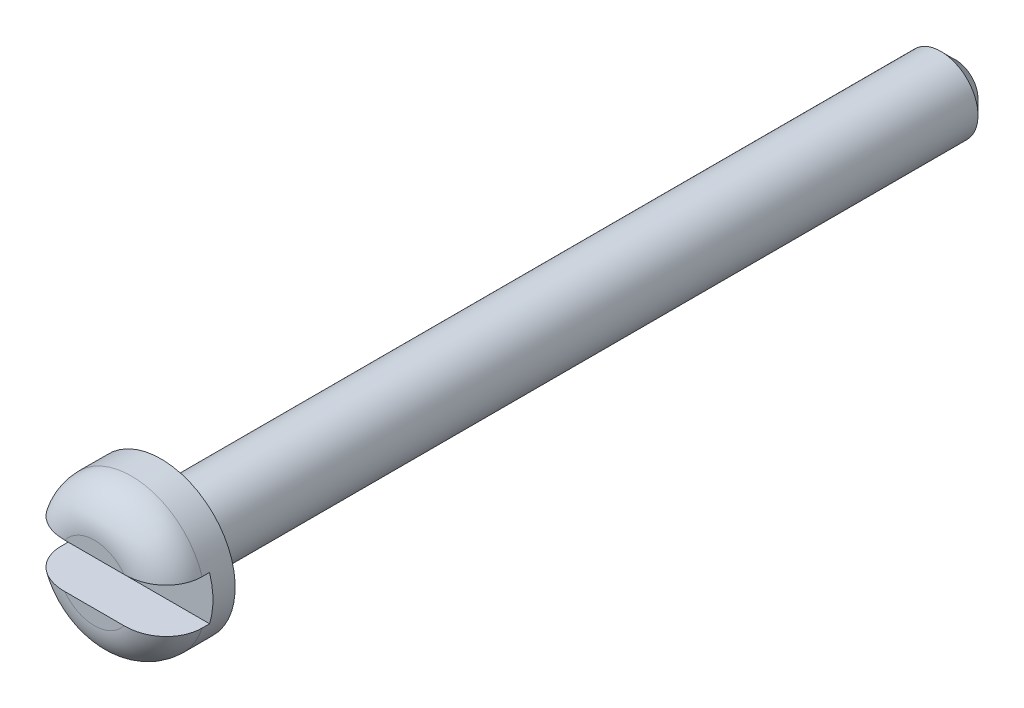
SolidWorks part; units mm, degrees
material "Простая углеродистая сталь"
ref_plane "Спереди" through (0, 0, 0) normal (0, 0, 1) x (1, 0, 0)
ref_plane "Сверху" through (0, 0, 0) normal (0, 1, 0) x (1, 0, 0)
ref_plane "Справа" through (0, 0, 0) normal (1, 0, 0) x (0, 0, -1)
sketch "Эскиз1" plane through (0, 0, 0) normal (0, 1, 0) x (1, 0, 0)
  line L0 (0, 0) -> (-2, 0)
  line L1 (-2, 0) -> (-2, 1.8)
  line L2 (-2, 1.8) -> (-1, 1.8)
  line L3 (-1, 1.8) -> (-1, 23.25)
  line L4 (-1, 23.25) -> (0, 23.25)
  line L5 (0, 23.25) -> (0, 0)
  dimension "D1" = 2
  dimension "D2" = 1.8
  dimension "D3" = 23.25
  dimension "D4" = 1
revolve "Повернуть1" add sketch "Эскиз1" angle 360 about L5
sketch "Эскиз2" plane through (0, 0, 0) normal (1, 0, 0) x (0, 0, -1)
  line L0 (0, 0) -> (22.6818, 0) construction
  line L1 (0, -0.6) -> (0, 0.6)
  line L2 (0, 0.6) -> (1.2, 0.6)
  line L3 (0, -0.6) -> (1.2, -0.6)
  line L4 (1.2, 0.6) -> (1.2, -0.6)
  point P7 (0, 0)
  point P10 (1.2, 0)
  dimension "D1" = 1.2
  dimension "D2" = 1.2
extrude "Вырез-Вытянуть1" cut sketch "Эскиз2" against normal through all both and the other way through all
chamfer "Фаска1" distance 0.4 angle 45 1 edges at (-1, 0, -23.25)
fillet "Скругление1" radius 1 2 edges at (0, -2, 0) (0, 2, 0)
fillet "Скругление2" radius 0.4 1 edges at (-1, 0, -1.8)
